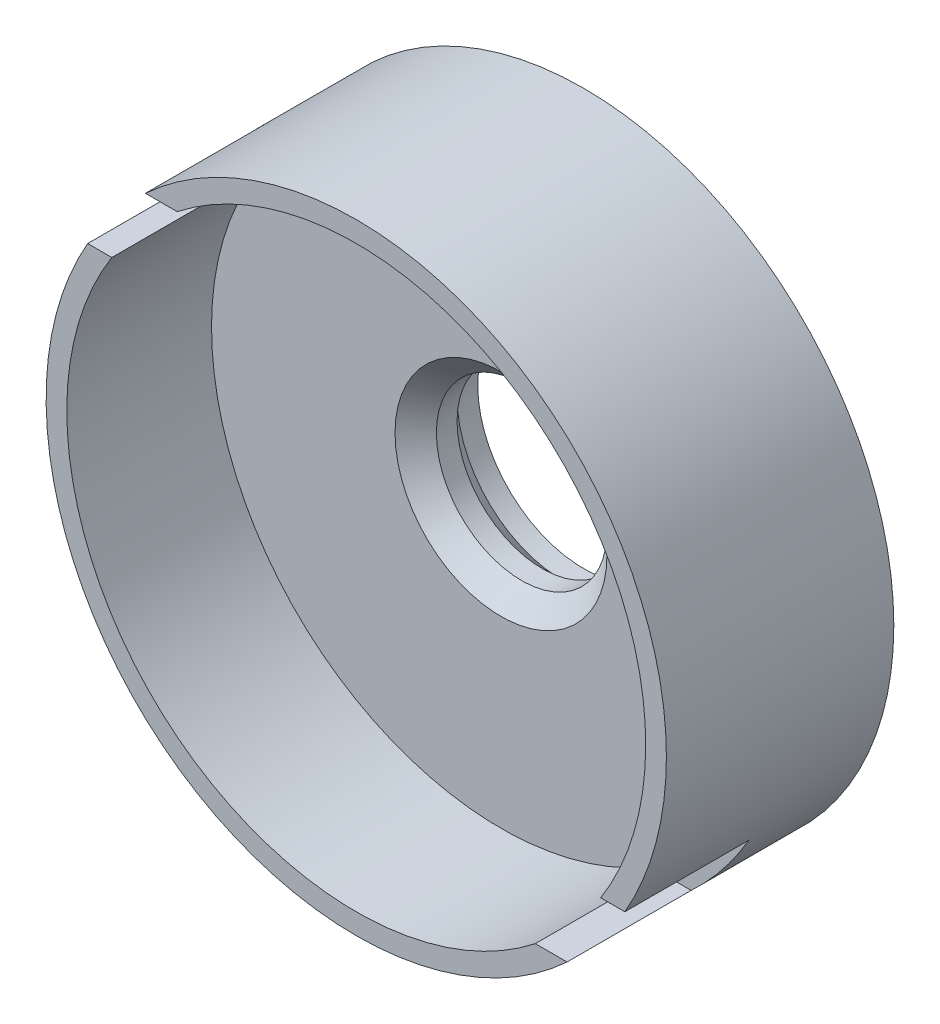
SolidWorks part; units mm, degrees
ref_plane "Спереди" through (0, 0, 0) normal (0, 0, 1) x (1, 0, 0)
ref_plane "Сверху" through (0, 0, 0) normal (0, 1, 0) x (1, 0, 0)
ref_plane "Справа" through (0, 0, 0) normal (1, 0, 0) x (0, 0, -1)
sketch "Эскиз5" plane through (0, 0, 0) normal (0, 0, 1) x (1, 0, 0)
  circle A0 centre (0, 0) radius 30
  dimension "D1" = 60
extrude "Бобышка-Вытянуть1" add sketch "Эскиз5" along normal blind 20 and the other way blind 2
sketch "Эскиз6" plane through (0, 0, 0) normal (0, 0, 1) x (1, 0, 0)
  circle A0 centre (0, 0) radius 28
  dimension "D1" = 56
extrude "Вырез-Вытянуть1" cut sketch "Эскиз6" along normal blind 14 from offset 6
sketch "Эскиз7" plane through (0, 0, 0) normal (0, 0, 1) x (1, 0, 0)
  circle A0 centre (0, 0) radius 8.25
  dimension "D1" = 16.5
extrude "Вырез-Вытянуть2" cut sketch "Эскиз7" along normal blind 15 and the other way blind 2
sketch "Эскиз8" plane through (0, 0, 0) normal (0, 0, 1) x (1, 0, 0)
  circle A0 centre (0, 0) radius 10.25
  dimension "D1" = 20.5
sketch "Эскиз10" plane through (0, 0, 0) normal (0, 0, 1) x (1, 0, 0)
  line L1 (-30, 15) -> (-15, 15)
  line L2 (-30, 15) -> (-30, 22)
  line L3 (-30, 22) -> (-15, 22)
  line L4 (-15, 15) -> (-15, 22)
  dimension "D1" = 15
  dimension "D2" = 15
  dimension "D3" = 7
  dimension "D4" = 15
extrude "Вырез-Вытянуть4" cut sketch "Эскиз10" along normal blind 12 from offset 8
sketch "Эскиз13" plane through (0, 0, 0) normal (0, 0, 1) x (1, 0, 0)
  line L1 (15, -15) -> (30, -15)
  line L2 (15, -15) -> (15, -22)
  line L3 (15, -22) -> (30, -22)
  line L4 (30, -15) -> (30, -22)
  dimension "D1" = 15
  dimension "D2" = 15
  dimension "D3" = 15
  dimension "D4" = 7
extrude "Вырез-Вытянуть5" cut sketch "Эскиз13" along normal blind 12 from offset 8
sketch "Эскиз14" plane through (0, 0, 0) normal (0, 0, 1) x (1, 0, 0)
  circle A0 centre (0, 0) radius 10.5
  dimension "D1" = 21
sketch "Эскиз15" plane through (0, 0, 0) normal (1, 0, 0) x (0, 0, -1)
  line L6 (0, 10.25) -> (0, -10.25) construction
  line L9 (0, 0) -> (-12.4767, 0) construction
  line L15 (-6, 8.25) -> (-4, 8.25)
  line L16 (2, 8.25) -> (-6, 8.25) construction
  line L17 (-4, 8.25) -> (-6, 10.25)
  line L18 (-6, 28) -> (-6, -28) construction
  line L19 (-6, 10.25) -> (-6, 8.25)
  line L20 (2, 8.25) -> (2, 10.25)
  line L21 (2, -30) -> (2, 30) construction
  line L22 (2, 10.25) -> (0, 10.25)
  line L23 (0, 10.25) -> (-2, 8.25)
  line L24 (-2, 8.25) -> (2, 8.25)
  dimension "D1" = 2
  dimension "D2" = 2
  dimension "D3" = 2
  dimension "D4" = 2
revolve "Вырез-Повернуть1" cut sketch "Эскиз15" angle 360 about L9
